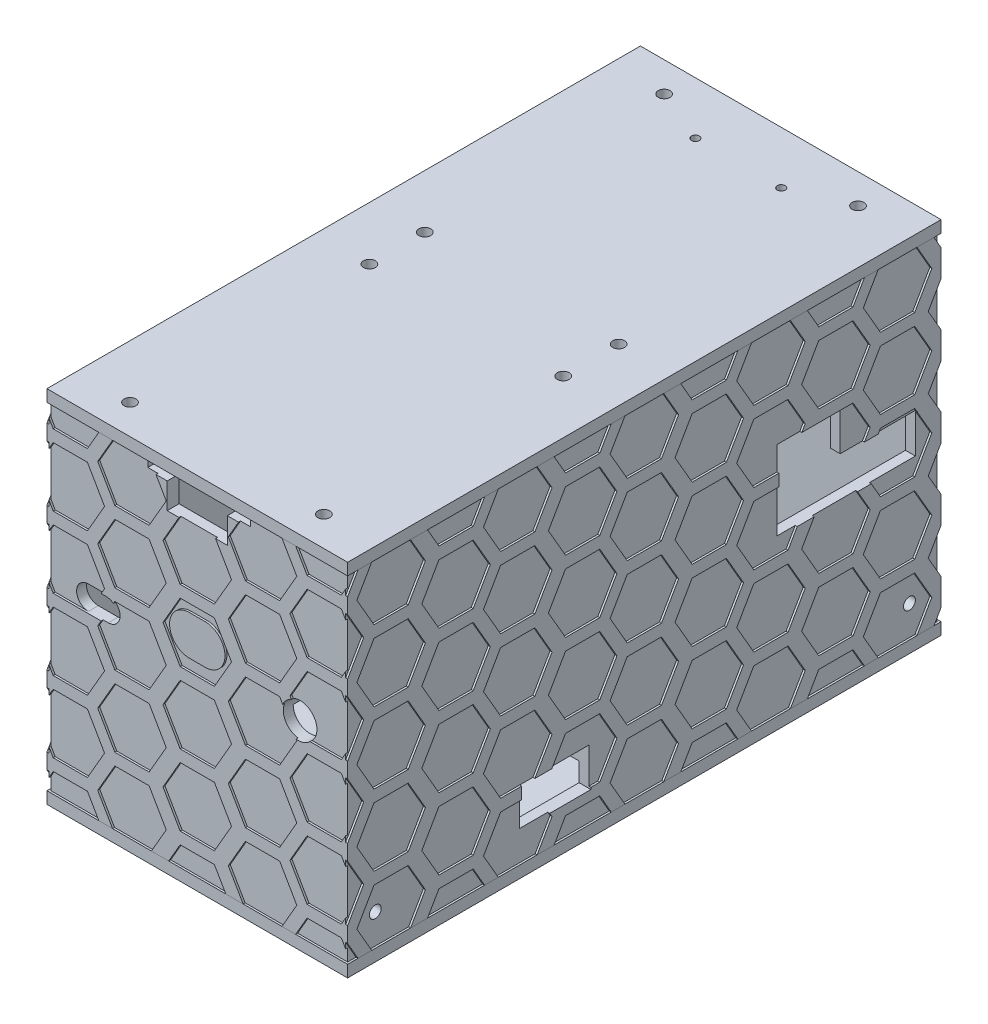
SolidWorks part; units mm, degrees
ref_plane "Front Plane" through (0, 0, 0) normal (0, 0, 1) x (1, 0, 0)
ref_plane "Top Plane" through (0, 0, 0) normal (0, 1, 0) x (1, 0, 0)
ref_plane "Right Plane" through (0, 0, 0) normal (1, 0, 0) x (0, 0, -1)
sketch "Sketch1" plane through (0, 0, 0) normal (0, 1, 0) x (1, 0, 0)
  line L0 (0, -67.5) -> (0, -72) construction
  line L1 (-38, 75) -> (38, 75)
  line L2 (-38, 75) -> (-38, -75)
  line L3 (-38, -75) -> (38, -75)
  line L4 (38, 75) -> (38, -75)
  line L5 (-38, 75) -> (38, -75) construction
  line L6 (-38, -75) -> (38, 75) construction
  line L7 (-24.5, -7) -> (24.5, -7) construction
  line L8 (-24.5, -7) -> (-24.5, -67.5) construction
  line L9 (-24.5, -67.5) -> (24.5, -67.5) construction
  line L10 (24.5, -7) -> (24.5, -67.5) construction
  line L11 (-24.5, -7) -> (24.5, -67.5) construction
  line L12 (-24.5, -67.5) -> (24.5, -7) construction
  line L13 (-35, -72) -> (35, -72) construction
  line L14 (-35, -72) -> (-35, 72) construction
  line L15 (-35, 72) -> (35, 72) construction
  line L16 (35, -72) -> (35, 72) construction
  line L17 (-35, -72) -> (35, 72) construction
  line L18 (-35, 72) -> (35, -72) construction
  line L19 (-35, 0) -> (35, 0) construction
  line L20 (-11.85, 61.75) -> (11.85, 61.75) construction
  line L21 (0, 61.75) -> (0, 75) construction
  line L22 (-10.85, 62.75) -> (-10.85, 75) construction
  circle A0 centre (-24.5, -7) radius 1.5
  circle A1 centre (24.5, -7) radius 1.5
  circle A2 centre (-24.5, -67.5) radius 1.5
  circle A3 centre (24.5, -67.5) radius 1.5
  circle A4 centre (-24.5, 67.5) radius 1.5
  circle A5 centre (24.5, 67.5) radius 1.5
  circle A6 centre (24.5, 7) radius 1.5
  circle A7 centre (-24.5, 7) radius 1.5
  circle A8 centre (-10.85, 61.75) radius 1
  circle A9 centre (10.85, 61.75) radius 1
  point P0 (0, 0)
  point P5 (0, -37.25)
  point P12 (0, 0)
  dimension "D9" = 3
  dimension "D10" = 2
  dimension "D8" = 23.7
  dimension "D11" = 2
  dimension "D1" = 76
  dimension "D2" = 150
  dimension "D3" = 49
  dimension "D4" = 60.5
  dimension "D5" = 3
  dimension "D6" = 3
  dimension "D7" = 4.5
  dimension "D12" = 12.25
extrude "Boss-Extrude1" add sketch "Sketch1" along normal blind 3
sketch "Sketch3" plane through (0, 0, 0) normal (0, -1, 0) x (1, 0, 0)
  line L0 (-38, 75) -> (-38, -75)
  line L1 (-38, 75) -> (38, 75)
  line L2 (38, 75) -> (38, -75)
  line L3 (38, -75) -> (-38, -75)
  line L4 (-35, 61.5) -> (-18.5, 61.5)
  line L5 (-18.5, 61.5) -> (-18.5, 72)
  line L6 (-18.5, 72) -> (18.5, 72)
  line L7 (18.5, 72) -> (18.5, 61.5)
  line L8 (18.5, 61.5) -> (35, 61.5)
  line L9 (35, 61.5) -> (35, 13)
  line L10 (35, 13) -> (18.5, 13)
  line L11 (18.5, 13) -> (18.5, -13)
  line L12 (18.5, -13) -> (35, -13)
  line L13 (35, -13) -> (35, -61.5)
  line L14 (35, -61.5) -> (18.5, -61.5)
  line L15 (18.5, -61.5) -> (18.5, -72)
  line L16 (18.5, -72) -> (-18.5, -72)
  line L17 (-18.5, -72) -> (-18.5, -61.5)
  line L18 (-18.5, -61.5) -> (-35, -61.5)
  line L19 (-35, -61.5) -> (-35, -13)
  line L20 (-35, -13) -> (-18.5, -13)
  line L21 (-18.5, -13) -> (-18.5, 13)
  line L22 (-18.5, 13) -> (-35, 13)
  line L23 (-35, 13) -> (-35, 61.5)
  circle A0 centre (-24.5, 67.5) radius 1.5 construction
  circle A1 centre (24.5, 67.5) radius 1.5 construction
  circle A2 centre (24.5, 7) radius 1.5 construction
  circle A3 centre (24.5, -7) radius 1.5 construction
  circle A4 centre (-24.5, 7) radius 1.5 construction
  circle A5 centre (-24.5, -7) radius 1.5 construction
  circle A6 centre (-24.5, -67.5) radius 1.5 construction
  circle A7 centre (24.5, -67.5) radius 1.5 construction
  circle A8 centre (-24.5, 67.5) radius 1.5
  circle A9 centre (24.5, 67.5) radius 1.5
  circle A10 centre (-24.5, 7) radius 1.5
  circle A11 centre (-24.5, -7) radius 1.5
  circle A12 centre (24.5, -7) radius 1.5
  circle A13 centre (24.5, 7) radius 1.5
  circle A14 centre (-24.5, -67.5) radius 1.5
  circle A19 centre (24.5, -67.5) radius 1.5
  dimension "D3" = 6
  dimension "D4" = 6
  dimension "D5" = 6
  dimension "D8" = 6
  dimension "D9" = 6
  dimension "D10" = 6
  dimension "D11" = 6
  dimension "D13" = 6
  dimension "D16" = 6
  dimension "D19" = 6
  dimension "D1" = 3
  dimension "D2" = 3
  dimension "D6" = 6
  dimension "D7" = 3
  dimension "D12" = 6
  dimension "D14" = 3
  dimension "D15" = 6
  dimension "D17" = 6
  dimension "D18" = 3
  dimension "D20" = 3
extrude "Boss-Extrude2" add sketch "Sketch3" along normal blind 3 separate body
sketch "Sketch4" plane through (0, -3, 0) normal (0, -1, 0) x (1, 0, 0)
  line L1 (38, 75) -> (38, -75)
  line L2 (38, -75) -> (-38, -75)
  line L3 (-38, -75) -> (-38, 75)
  line L4 (18.5, 72) -> (-18.5, 72)
  line L5 (-18.5, 72) -> (-35, 72)
  line L6 (-35, 72) -> (-35, 61.5)
  line L7 (-35, 61.5) -> (-35, -61.5)
  line L8 (-35, -61.5) -> (-35, -72)
  line L9 (-35, -72) -> (18.5, -72)
  line L10 (18.5, -72) -> (35, -72)
  line L11 (35, -72) -> (35, -61.5)
  line L12 (35, -61.5) -> (35, 61.5)
  line L13 (35, 61.5) -> (35, 72)
  line L14 (35, 72) -> (18.5, 72)
  line L15 (-38, 75) -> (38, 75)
extrude "Boss-Extrude3" add sketch "Sketch4" along normal blind 82
sketch "Sketch6" plane through (0, 0, -75) normal (0, 0, -1) x (-1, 0, 0)
  line L0 (0, 0) -> (0, -33) construction
  line L1 (-2, -33) -> (2, -33) construction
  line L2 (-2, -28) -> (2, -28)
  line L3 (-2, -38) -> (2, -38)
  line L4 (-2, -33) -> (-7, -33) construction
  line L5 (2, -33) -> (7, -33) construction
  arc A0 (-2, -28) -> (-2, -38) centre (-2, -33) ccw
  arc A1 (2, -38) -> (2, -28) centre (2, -33) ccw
  point P5 (0, -33)
  dimension "D1" = 10
  dimension "D2" = 14
  dimension "D3" = 28
extrude "Cut-Extrude1" cut sketch "Sketch6" against normal up to surface (3 mm away) up to face at (0, -22.75, -72)
sketch "Sketch7" plane through (0, 0, 75) normal (0, 0, 1) x (1, 0, 0)
  line L0 (0, 0) -> (13, 0)
  line L1 (-38, 0) -> (38, 0) construction
  line L2 (13, 0) -> (13, -2)
  line L3 (13, -2) -> (7.6, -2)
  line L4 (7.6, -2) -> (7.6, -8.5)
  line L5 (7.6, -8.5) -> (-7.6, -8.5)
  line L6 (-7.6, -8.5) -> (-7.6, -2)
  line L7 (-7.6, -2) -> (-13, -2)
  line L8 (-13, -2) -> (-13, 0)
  line L9 (38, 0) -> (-38, 0) construction
  line L10 (-13, 0) -> (0, 0)
  line L11 (0, 0) -> (0, -8.5) construction
  dimension "D1" = 15.2
  dimension "D2" = 6.5
  dimension "D3" = 2
  dimension "D4" = 5.4
extrude "Cut-Extrude2" cut sketch "Sketch7" against normal up to surface (3 mm away) up to face at (0, -22.75, 72)
sketch "Sketch8" plane through (38, 0, 0) normal (1, 0, 0) x (0, 0, -1)
  line L0 (-75, -85) -> (-75, 0) construction
  line L1 (-31, -68) -> (-13.5, -68)
  line L2 (-31, -68) -> (-31, -77.5)
  line L3 (-31, -77.5) -> (-13.5, -77.5)
  line L4 (-13.5, -68) -> (-13.5, -77.5)
  line L5 (-31, -68) -> (-13.5, -77.5) construction
  line L6 (-31, -77.5) -> (-13.5, -68) construction
  line L7 (-75, 0) -> (75, 0) construction
  point P0 (-22.25, -72.75)
  dimension "D1" = 44
  dimension "D2" = 68
  dimension "D3" = 17.5
  dimension "D4" = 9.5
extrude "Cut-Extrude3" cut sketch "Sketch8" against normal up to surface (3 mm away) up to face at (35, -15.6667, 0)
sketch "Sketch9" plane through (38, 0, 0) normal (1, 0, 0) x (0, 0, -1)
  line L0 (-31, -72.75) -> (-33, -72.75)
  line L1 (-31, -68) -> (-31, -77.5) construction
  line L2 (-33, -72.75) -> (-33, -66)
  line L3 (-33, -66) -> (-11.5, -66)
  line L4 (-11.5, -66) -> (-11.5, -72.75)
  line L5 (-11.5, -72.75) -> (-13.5, -72.75)
  line L6 (-13.5, -77.5) -> (-13.5, -68) construction
  line L7 (-13.5, -72.75) -> (-13.5, -68)
  line L8 (-13.5, -68) -> (-31, -68)
  line L9 (-31, -68) -> (-31, -72.75)
  dimension "D1" = 2
  dimension "D2" = 2
extrude "Boss-Extrude4" add sketch "Sketch9" against normal blind 10
sketch "Sketch12" plane through (0, 0, 75) normal (0, 0, 1) x (1, 0, 0)
  line L0 (-28, -35) -> (-23, -35)
  line L1 (-28, -41) -> (-23, -41)
  line L2 (-31, -38) -> (-20, -38) construction
  line L3 (-38, 0) -> (38, 0) construction
  line L4 (-25.5, 0) -> (-25.5, -35) construction
  line L5 (-13, 0) -> (-38, 0) construction
  line L6 (25.5, -38) -> (25.5, 0) construction
  line L7 (38, 0) -> (13, 0) construction
  arc A0 (-28, -35) -> (-28, -41) centre (-28, -38) ccw
  arc A1 (-23, -41) -> (-23, -35) centre (-23, -38) ccw
  circle A2 centre (25.5, -38) radius 4.25
  dimension "D1" = 6
  dimension "D4" = 8.5
  dimension "D2" = 11
  dimension "D3" = 35
extrude "Cut-Extrude4" cut sketch "Sketch12" against normal up to surface (3 mm away) up to face at (0, -12.9375, 72)
sketch "Sketch13" plane through (0, 0, 75) normal (0, 0, 1) x (1, 0, 0)
  line L0 (21.25, -38) -> (19.25, -38)
  line L1 (19.25, -38) -> (19.25, -31.75)
  line L2 (19.25, -31.75) -> (38, -31.75)
  line L3 (38, -85) -> (38, 0) construction
  line L4 (38, -31.75) -> (38, -38)
  line L5 (38, -38) -> (29.75, -38)
  line L6 (25.5, -33.75) -> (25.5, -31.75) construction
  circle A0 centre (25.5, -38) radius 4.25 construction
  arc A1 (29.75, -38) -> (21.25, -38) centre (25.5, -38) ccw
  dimension "D1" = 2
extrude "Boss-Extrude7" add sketch "Sketch13" against normal blind 10
ref_plane "Plane1" through (0, 0, 50) normal (0, 0, 1) x (1, 0, 0)
sketch "Sketch15" plane through (0, 0, 50) normal (0, 0, 1) x (1, 0, 0)
  line L0 (22.3, -38) -> (20.3, -38)
  line L1 (20.3, -38) -> (20.3, -32.8)
  line L2 (20.3, -32.8) -> (38, -32.8)
  line L3 (38, -85) -> (38, 0) construction
  line L4 (38, -32.8) -> (38, -38)
  line L5 (38, -38) -> (28.7, -38) construction
  line L6 (25.5, -34.8) -> (25.5, -32.8) construction
  line L10 (28.7, -38) -> (28.7, -43)
  line L11 (28.7, -43) -> (38, -43)
  line L12 (38, -43) -> (38, -38)
  arc A0 (28.7, -38) -> (22.3, -38) centre (25.5, -38) ccw
  circle A1 centre (25.5, -38) radius 4.25 construction
  dimension "D1" = 6.4
  dimension "D2" = 2
  dimension "D3" = 5
extrude "Boss-Extrude8" add sketch "Sketch15" against normal blind 2
chamfer "Chamfer1" distance 12 angle 45 1 edges at (35, -32.8, 49)
chamfer "Chamfer2" distance 2 angle 45 2 edges at (35, -31.9, 50) (35, -31.9, 48)
sketch "Sketch16" plane through (38, 0, 0) normal (1, 0, 0) x (0, 0, -1)
  line L0 (-67.5, -77.5) -> (-67.5, 0) construction
  line L1 (75, 0) -> (-75, 0) construction
  line L2 (-66, 0) -> (-69, 0) construction
  line L3 (69, 0) -> (66, 0) construction
  line L4 (75, -85) -> (-75, -85) construction
  line L5 (67.5, 0) -> (67.5, -77.5) construction
  line L6 (-67.5, -77.5) -> (67.5, -77.5) construction
  circle A0 centre (-67.5, -77.5) radius 1.5
  circle A1 centre (67.5, -77.5) radius 1.5
  dimension "D1" = 3
  dimension "D2" = 7.5
extrude "Cut-Extrude5" cut sketch "Sketch16" against normal through all and the other way through all
ref_plane "Plane2" through (0, 0, 0) normal (-1, 0, 0) x (0, 0, 1)
sketch "Sketch17" plane through (-38, 0, 0) normal (-1, 0, 0) x (0, 0, 1)
  line L0 (0, -42.5) -> (0, 0) construction
  line L1 (8.6603, -42.5) -> (4.3301, -35)
  line L2 (4.3301, -35) -> (-4.3301, -35)
  line L3 (-4.3301, -35) -> (-8.6603, -42.5)
  line L4 (-8.6603, -42.5) -> (-4.3301, -50)
  line L5 (-4.3301, -50) -> (4.3301, -50)
  line L6 (4.3301, -50) -> (8.6603, -42.5)
  line L7 (0, -42.5) -> (75, -42.5) construction
  line L8 (75, -85) -> (75, 0) construction
  line L9 (19.9186, -80) -> (24.2487, -87.5)
  line L10 (8.6603, -24.5) -> (4.3301, -17)
  line L11 (4.3301, -17) -> (-4.3301, -17)
  line L12 (-4.3301, -17) -> (-8.6603, -24.5)
  line L13 (-8.6603, -24.5) -> (-4.3301, -32)
  line L14 (-4.3301, -32) -> (4.3301, -32)
  line L15 (4.3301, -32) -> (8.6603, -24.5)
  line L16 (8.6603, -6.5) -> (4.3301, 1)
  line L17 (4.3301, 1) -> (-4.3301, 1)
  line L18 (-4.3301, 1) -> (-8.6603, -6.5)
  line L19 (-8.6603, -6.5) -> (-4.3301, -14)
  line L20 (-4.3301, -14) -> (4.3301, -14)
  line L21 (4.3301, -14) -> (8.6603, -6.5)
  line L22 (24.2487, -15.5) -> (19.9186, -8)
  line L23 (19.9186, -8) -> (11.2583, -8)
  line L24 (11.2583, -8) -> (6.9282, -15.5)
  line L25 (6.9282, -15.5) -> (11.2583, -23)
  line L26 (11.2583, -23) -> (19.9186, -23)
  line L27 (19.9186, -23) -> (24.2487, -15.5)
  line L28 (24.2487, -33.5) -> (19.9186, -26)
  line L29 (19.9186, -26) -> (11.2583, -26)
  line L30 (11.2583, -26) -> (6.9282, -33.5)
  line L31 (6.9282, -33.5) -> (11.2583, -41)
  line L32 (11.2583, -41) -> (19.9186, -41)
  line L33 (19.9186, -41) -> (24.2487, -33.5)
  line L34 (24.2487, 2.5) -> (19.9186, 10)
  line L35 (19.9186, 10) -> (11.2583, 10)
  line L36 (11.2583, 10) -> (6.9282, 2.5)
  line L37 (6.9282, 2.5) -> (11.2583, -5)
  line L38 (11.2583, -5) -> (19.9186, -5)
  line L39 (19.9186, -5) -> (24.2487, 2.5)
  line L40 (11.2583, -80) -> (19.9186, -80)
  line L41 (6.9282, -87.5) -> (11.2583, -80)
  line L42 (11.2583, -95) -> (6.9282, -87.5)
  line L43 (19.9186, -95) -> (11.2583, -95)
  line L44 (24.2487, -87.5) -> (19.9186, -95)
  line L45 (19.9186, -44) -> (24.2487, -51.5)
  line L46 (11.2583, -44) -> (19.9186, -44)
  line L47 (6.9282, -51.5) -> (11.2583, -44)
  line L48 (11.2583, -59) -> (6.9282, -51.5)
  line L49 (19.9186, -59) -> (11.2583, -59)
  line L50 (24.2487, -51.5) -> (19.9186, -59)
  line L51 (19.9186, -62) -> (24.2487, -69.5)
  line L52 (11.2583, -62) -> (19.9186, -62)
  line L53 (6.9282, -69.5) -> (11.2583, -62)
  line L54 (11.2583, -77) -> (6.9282, -69.5)
  line L55 (19.9186, -77) -> (11.2583, -77)
  line L56 (24.2487, -69.5) -> (19.9186, -77)
  line L57 (4.3301, -71) -> (8.6603, -78.5)
  line L58 (-4.3301, -71) -> (4.3301, -71)
  line L59 (-8.6603, -78.5) -> (-4.3301, -71)
  line L60 (-4.3301, -86) -> (-8.6603, -78.5)
  line L61 (4.3301, -86) -> (-4.3301, -86)
  line L62 (8.6603, -78.5) -> (4.3301, -86)
  line L63 (4.3301, -53) -> (8.6603, -60.5)
  line L64 (-4.3301, -53) -> (4.3301, -53)
  line L65 (-8.6603, -60.5) -> (-4.3301, -53)
  line L66 (-4.3301, -68) -> (-8.6603, -60.5)
  line L67 (4.3301, -68) -> (-4.3301, -68)
  line L68 (8.6603, -60.5) -> (4.3301, -68)
  line L69 (51.9186, 10) -> (43.2583, 10)
  line L70 (56.2487, 2.5) -> (51.9186, 10)
  line L71 (51.9186, -5) -> (56.2487, 2.5)
  line L72 (36.3301, 1) -> (27.6699, 1)
  line L73 (40.6603, -6.5) -> (36.3301, 1)
  line L74 (27.6699, 1) -> (23.3397, -6.5)
  line L75 (36.3301, -14) -> (40.6603, -6.5)
  line L76 (43.2583, 10) -> (38.9282, 2.5)
  line L77 (38.9282, 2.5) -> (43.2583, -5)
  line L78 (43.2583, -5) -> (51.9186, -5)
  line L79 (23.3397, -6.5) -> (27.6699, -14)
  line L80 (27.6699, -14) -> (36.3301, -14)
  line L81 (51.9186, -8) -> (43.2583, -8)
  line L82 (43.2583, -8) -> (38.9282, -15.5)
  line L83 (38.9282, -15.5) -> (43.2583, -23)
  line L84 (43.2583, -23) -> (51.9186, -23)
  line L85 (51.9186, -23) -> (56.2487, -15.5)
  line L86 (56.2487, -15.5) -> (51.9186, -8)
  line L87 (36.3301, -17) -> (27.6699, -17)
  line L88 (40.6603, -24.5) -> (36.3301, -17)
  line L89 (27.6699, -17) -> (23.3397, -24.5)
  line L90 (23.3397, -24.5) -> (27.6699, -32)
  line L91 (27.6699, -32) -> (36.3301, -32)
  line L92 (36.3301, -32) -> (40.6603, -24.5)
  line L93 (43.2583, -26) -> (38.9282, -33.5)
  line L94 (38.9282, -33.5) -> (43.2583, -41)
  line L95 (51.9186, -26) -> (43.2583, -26)
  line L96 (56.2487, -33.5) -> (51.9186, -26)
  line L97 (51.9186, -41) -> (56.2487, -33.5)
  line L98 (43.2583, -41) -> (51.9186, -41)
  line L99 (40.6603, -42.5) -> (36.3301, -35)
  line L100 (36.3301, -35) -> (27.6699, -35)
  line L101 (27.6699, -35) -> (23.3397, -42.5)
  line L102 (23.3397, -42.5) -> (27.6699, -50)
  line L103 (43.2583, -44) -> (51.9186, -44)
  line L104 (36.3301, -50) -> (40.6603, -42.5)
  line L105 (27.6699, -50) -> (36.3301, -50)
  line L106 (38.9282, -51.5) -> (43.2583, -44)
  line L107 (43.2583, -59) -> (38.9282, -51.5)
  line L108 (51.9186, -59) -> (43.2583, -59)
  line L109 (56.2487, -51.5) -> (51.9186, -59)
  line L110 (51.9186, -44) -> (56.2487, -51.5)
  line L111 (36.3301, -53) -> (40.6603, -60.5)
  line L112 (27.6699, -53) -> (36.3301, -53)
  line L113 (23.3397, -60.5) -> (27.6699, -53)
  line L114 (27.6699, -68) -> (23.3397, -60.5)
  line L115 (36.3301, -68) -> (27.6699, -68)
  line L116 (40.6603, -60.5) -> (36.3301, -68)
  line L117 (43.2583, -62) -> (51.9186, -62)
  line L118 (38.9282, -69.5) -> (43.2583, -62)
  line L119 (51.9186, -62) -> (56.2487, -69.5)
  line L120 (56.2487, -69.5) -> (51.9186, -77)
  line L121 (51.9186, -77) -> (43.2583, -77)
  line L122 (43.2583, -77) -> (38.9282, -69.5)
  line L123 (36.3301, -71) -> (40.6603, -78.5)
  line L124 (27.6699, -71) -> (36.3301, -71)
  line L125 (23.3397, -78.5) -> (27.6699, -71)
  line L126 (27.6699, -86) -> (23.3397, -78.5)
  line L127 (36.3301, -86) -> (27.6699, -86)
  line L128 (40.6603, -78.5) -> (36.3301, -86)
  line L129 (38.9282, -87.5) -> (43.2583, -80)
  line L130 (43.2583, -95) -> (38.9282, -87.5)
  line L131 (51.9186, -95) -> (43.2583, -95)
  line L132 (56.2487, -87.5) -> (51.9186, -95)
  line L133 (51.9186, -80) -> (56.2487, -87.5)
  line L134 (43.2583, -80) -> (51.9186, -80)
  line L135 (83.9186, 10) -> (75.2583, 10)
  line L136 (88.2487, 2.5) -> (83.9186, 10)
  line L137 (83.9186, -5) -> (88.2487, 2.5)
  line L138 (68.3301, 1) -> (59.6699, 1)
  line L139 (72.6603, -6.5) -> (68.3301, 1)
  line L140 (59.6699, 1) -> (55.3397, -6.5)
  line L141 (68.3301, -14) -> (72.6603, -6.5)
  line L142 (75.2583, 10) -> (70.9282, 2.5)
  line L143 (70.9282, 2.5) -> (75.2583, -5)
  line L144 (75.2583, -5) -> (83.9186, -5)
  line L145 (55.3397, -6.5) -> (59.6699, -14)
  line L146 (59.6699, -14) -> (68.3301, -14)
  line L147 (83.9186, -8) -> (75.2583, -8)
  line L148 (75.2583, -8) -> (70.9282, -15.5)
  line L149 (70.9282, -15.5) -> (75.2583, -23)
  line L150 (75.2583, -23) -> (83.9186, -23)
  line L151 (83.9186, -23) -> (88.2487, -15.5)
  line L152 (88.2487, -15.5) -> (83.9186, -8)
  line L153 (68.3301, -17) -> (59.6699, -17)
  line L154 (72.6603, -24.5) -> (68.3301, -17)
  line L155 (59.6699, -17) -> (55.3397, -24.5)
  line L156 (55.3397, -24.5) -> (59.6699, -32)
  line L157 (59.6699, -32) -> (68.3301, -32)
  line L158 (68.3301, -32) -> (72.6603, -24.5)
  line L159 (75.2583, -26) -> (70.9282, -33.5)
  line L160 (70.9282, -33.5) -> (75.2583, -41)
  line L161 (83.9186, -26) -> (75.2583, -26)
  line L162 (88.2487, -33.5) -> (83.9186, -26)
  line L163 (83.9186, -41) -> (88.2487, -33.5)
  line L164 (75.2583, -41) -> (83.9186, -41)
  line L165 (72.6603, -42.5) -> (68.3301, -35)
  line L166 (68.3301, -35) -> (59.6699, -35)
  line L167 (59.6699, -35) -> (55.3397, -42.5)
  line L168 (55.3397, -42.5) -> (59.6699, -50)
  line L169 (75.2583, -44) -> (83.9186, -44)
  line L170 (68.3301, -50) -> (72.6603, -42.5)
  line L171 (59.6699, -50) -> (68.3301, -50)
  line L172 (70.9282, -51.5) -> (75.2583, -44)
  line L173 (75.2583, -59) -> (70.9282, -51.5)
  line L174 (83.9186, -59) -> (75.2583, -59)
  line L175 (88.2487, -51.5) -> (83.9186, -59)
  line L176 (83.9186, -44) -> (88.2487, -51.5)
  line L177 (68.3301, -53) -> (72.6603, -60.5)
  line L178 (59.6699, -53) -> (68.3301, -53)
  line L179 (55.3397, -60.5) -> (59.6699, -53)
  line L180 (59.6699, -68) -> (55.3397, -60.5)
  line L181 (68.3301, -68) -> (59.6699, -68)
  line L182 (72.6603, -60.5) -> (68.3301, -68)
  line L183 (75.2583, -62) -> (83.9186, -62)
  line L184 (70.9282, -69.5) -> (75.2583, -62)
  line L185 (83.9186, -62) -> (88.2487, -69.5)
  line L186 (88.2487, -69.5) -> (83.9186, -77)
  line L187 (83.9186, -77) -> (75.2583, -77)
  line L188 (75.2583, -77) -> (70.9282, -69.5)
  line L189 (68.3301, -71) -> (72.6603, -78.5)
  line L190 (59.6699, -71) -> (68.3301, -71)
  line L191 (55.3397, -78.5) -> (59.6699, -71)
  line L192 (59.6699, -86) -> (55.3397, -78.5)
  line L193 (68.3301, -86) -> (59.6699, -86)
  line L194 (72.6603, -78.5) -> (68.3301, -86)
  line L195 (70.9282, -87.5) -> (75.2583, -80)
  line L196 (75.2583, -95) -> (70.9282, -87.5)
  line L197 (83.9186, -95) -> (75.2583, -95)
  line L198 (88.2487, -87.5) -> (83.9186, -95)
  line L199 (83.9186, -80) -> (88.2487, -87.5)
  line L200 (75.2583, -80) -> (83.9186, -80)
  line L201 (19.9186, 10) -> (11.2583, 10)
  line L202 (24.2487, 2.5) -> (19.9186, 10)
  line L203 (19.9186, -5) -> (24.2487, 2.5)
  line L204 (4.3301, 1) -> (-4.3301, 1)
  line L205 (8.6603, -6.5) -> (4.3301, 1)
  line L206 (-4.3301, 1) -> (-8.6603, -6.5)
  line L207 (4.3301, -14) -> (8.6603, -6.5)
  line L208 (11.2583, 10) -> (6.9282, 2.5)
  line L209 (6.9282, 2.5) -> (11.2583, -5)
  line L210 (11.2583, -5) -> (19.9186, -5)
  line L211 (-8.6603, -6.5) -> (-4.3301, -14)
  line L212 (-4.3301, -14) -> (4.3301, -14)
  line L213 (19.9186, -8) -> (11.2583, -8)
  line L214 (11.2583, -8) -> (6.9282, -15.5)
  line L215 (6.9282, -15.5) -> (11.2583, -23)
  line L216 (11.2583, -23) -> (19.9186, -23)
  line L217 (19.9186, -23) -> (24.2487, -15.5)
  line L218 (24.2487, -15.5) -> (19.9186, -8)
  line L219 (4.3301, -17) -> (-4.3301, -17)
  line L220 (8.6603, -24.5) -> (4.3301, -17)
  line L221 (-4.3301, -17) -> (-8.6603, -24.5)
  line L222 (-8.6603, -24.5) -> (-4.3301, -32)
  line L223 (-4.3301, -32) -> (4.3301, -32)
  line L224 (4.3301, -32) -> (8.6603, -24.5)
  line L225 (11.2583, -26) -> (6.9282, -33.5)
  line L226 (6.9282, -33.5) -> (11.2583, -41)
  line L227 (19.9186, -26) -> (11.2583, -26)
  line L228 (24.2487, -33.5) -> (19.9186, -26)
  line L229 (19.9186, -41) -> (24.2487, -33.5)
  line L230 (11.2583, -41) -> (19.9186, -41)
  line L231 (8.6603, -42.5) -> (4.3301, -35)
  line L232 (4.3301, -35) -> (-4.3301, -35)
  line L233 (-4.3301, -35) -> (-8.6603, -42.5)
  line L234 (-8.6603, -42.5) -> (-4.3301, -50)
  line L235 (11.2583, -44) -> (19.9186, -44)
  line L236 (4.3301, -50) -> (8.6603, -42.5)
  line L237 (-4.3301, -50) -> (4.3301, -50)
  line L238 (6.9282, -51.5) -> (11.2583, -44)
  line L239 (11.2583, -59) -> (6.9282, -51.5)
  line L240 (19.9186, -59) -> (11.2583, -59)
  line L241 (24.2487, -51.5) -> (19.9186, -59)
  line L242 (19.9186, -44) -> (24.2487, -51.5)
  line L243 (4.3301, -53) -> (8.6603, -60.5)
  line L244 (-4.3301, -53) -> (4.3301, -53)
  line L245 (-8.6603, -60.5) -> (-4.3301, -53)
  line L246 (-4.3301, -68) -> (-8.6603, -60.5)
  line L247 (4.3301, -68) -> (-4.3301, -68)
  line L248 (8.6603, -60.5) -> (4.3301, -68)
  line L249 (11.2583, -62) -> (19.9186, -62)
  line L250 (6.9282, -69.5) -> (11.2583, -62)
  line L251 (19.9186, -62) -> (24.2487, -69.5)
  line L252 (24.2487, -69.5) -> (19.9186, -77)
  line L253 (19.9186, -77) -> (11.2583, -77)
  line L254 (11.2583, -77) -> (6.9282, -69.5)
  line L255 (4.3301, -71) -> (8.6603, -78.5)
  line L256 (-4.3301, -71) -> (4.3301, -71)
  line L257 (-8.6603, -78.5) -> (-4.3301, -71)
  line L258 (-4.3301, -86) -> (-8.6603, -78.5)
  line L259 (4.3301, -86) -> (-4.3301, -86)
  line L260 (8.6603, -78.5) -> (4.3301, -86)
  line L261 (6.9282, -87.5) -> (11.2583, -80)
  line L262 (11.2583, -95) -> (6.9282, -87.5)
  line L263 (19.9186, -95) -> (11.2583, -95)
  line L264 (24.2487, -87.5) -> (19.9186, -95)
  line L265 (19.9186, -80) -> (24.2487, -87.5)
  line L266 (11.2583, -80) -> (19.9186, -80)
  line L267 (51.9186, 10) -> (43.2583, 10)
  line L268 (56.2487, 2.5) -> (51.9186, 10)
  line L269 (51.9186, -5) -> (56.2487, 2.5)
  line L270 (36.3301, 1) -> (27.6699, 1)
  line L271 (40.6603, -6.5) -> (36.3301, 1)
  line L272 (27.6699, 1) -> (23.3397, -6.5)
  line L273 (36.3301, -14) -> (40.6603, -6.5)
  line L274 (43.2583, 10) -> (38.9282, 2.5)
  line L275 (38.9282, 2.5) -> (43.2583, -5)
  line L276 (43.2583, -5) -> (51.9186, -5)
  line L277 (23.3397, -6.5) -> (27.6699, -14)
  line L278 (27.6699, -14) -> (36.3301, -14)
  line L279 (51.9186, -8) -> (43.2583, -8)
  line L280 (43.2583, -8) -> (38.9282, -15.5)
  line L281 (38.9282, -15.5) -> (43.2583, -23)
  line L282 (43.2583, -23) -> (51.9186, -23)
  line L283 (51.9186, -23) -> (56.2487, -15.5)
  line L284 (56.2487, -15.5) -> (51.9186, -8)
  line L285 (36.3301, -17) -> (27.6699, -17)
  line L286 (40.6603, -24.5) -> (36.3301, -17)
  line L287 (27.6699, -17) -> (23.3397, -24.5)
  line L288 (23.3397, -24.5) -> (27.6699, -32)
  line L289 (27.6699, -32) -> (36.3301, -32)
  line L290 (36.3301, -32) -> (40.6603, -24.5)
  line L291 (43.2583, -26) -> (38.9282, -33.5)
  line L292 (38.9282, -33.5) -> (43.2583, -41)
  line L293 (51.9186, -26) -> (43.2583, -26)
  line L294 (56.2487, -33.5) -> (51.9186, -26)
  line L295 (51.9186, -41) -> (56.2487, -33.5)
  line L296 (43.2583, -41) -> (51.9186, -41)
  line L297 (40.6603, -42.5) -> (36.3301, -35)
  line L298 (36.3301, -35) -> (27.6699, -35)
  line L299 (27.6699, -35) -> (23.3397, -42.5)
  line L300 (23.3397, -42.5) -> (27.6699, -50)
  line L301 (43.2583, -44) -> (51.9186, -44)
  line L302 (36.3301, -50) -> (40.6603, -42.5)
  line L303 (27.6699, -50) -> (36.3301, -50)
  line L304 (38.9282, -51.5) -> (43.2583, -44)
  line L305 (43.2583, -59) -> (38.9282, -51.5)
  line L306 (51.9186, -59) -> (43.2583, -59)
  line L307 (56.2487, -51.5) -> (51.9186, -59)
  line L308 (51.9186, -44) -> (56.2487, -51.5)
  line L309 (36.3301, -53) -> (40.6603, -60.5)
  line L310 (27.6699, -53) -> (36.3301, -53)
  line L311 (23.3397, -60.5) -> (27.6699, -53)
  line L312 (27.6699, -68) -> (23.3397, -60.5)
  line L313 (36.3301, -68) -> (27.6699, -68)
  line L314 (40.6603, -60.5) -> (36.3301, -68)
  line L315 (43.2583, -62) -> (51.9186, -62)
  line L316 (38.9282, -69.5) -> (43.2583, -62)
  line L317 (51.9186, -62) -> (56.2487, -69.5)
  line L318 (56.2487, -69.5) -> (51.9186, -77)
  line L319 (51.9186, -77) -> (43.2583, -77)
  line L320 (43.2583, -77) -> (38.9282, -69.5)
  line L321 (36.3301, -71) -> (40.6603, -78.5)
  line L322 (27.6699, -71) -> (36.3301, -71)
  line L323 (23.3397, -78.5) -> (27.6699, -71)
  line L324 (27.6699, -86) -> (23.3397, -78.5)
  line L325 (36.3301, -86) -> (27.6699, -86)
  line L326 (40.6603, -78.5) -> (36.3301, -86)
  line L327 (38.9282, -87.5) -> (43.2583, -80)
  line L328 (43.2583, -95) -> (38.9282, -87.5)
  line L329 (51.9186, -95) -> (43.2583, -95)
  line L330 (56.2487, -87.5) -> (51.9186, -95)
  line L331 (51.9186, -80) -> (56.2487, -87.5)
  line L332 (43.2583, -80) -> (51.9186, -80)
  line L333 (-12.0814, 10) -> (-20.7417, 10)
  line L334 (-7.7513, 2.5) -> (-12.0814, 10)
  line L335 (-12.0814, -5) -> (-7.7513, 2.5)
  line L336 (-27.6699, 1) -> (-36.3301, 1)
  line L337 (-23.3397, -6.5) -> (-27.6699, 1)
  line L338 (-36.3301, 1) -> (-40.6603, -6.5)
  line L339 (-27.6699, -14) -> (-23.3397, -6.5)
  line L340 (-20.7417, 10) -> (-25.0718, 2.5)
  line L341 (-25.0718, 2.5) -> (-20.7417, -5)
  line L342 (-20.7417, -5) -> (-12.0814, -5)
  line L343 (-40.6603, -6.5) -> (-36.3301, -14)
  line L344 (-36.3301, -14) -> (-27.6699, -14)
  line L345 (-12.0814, -8) -> (-20.7417, -8)
  line L346 (-20.7417, -8) -> (-25.0718, -15.5)
  line L347 (-25.0718, -15.5) -> (-20.7417, -23)
  line L348 (-20.7417, -23) -> (-12.0814, -23)
  line L349 (-12.0814, -23) -> (-7.7513, -15.5)
  line L350 (-7.7513, -15.5) -> (-12.0814, -8)
  line L351 (-27.6699, -17) -> (-36.3301, -17)
  line L352 (-23.3397, -24.5) -> (-27.6699, -17)
  line L353 (-36.3301, -17) -> (-40.6603, -24.5)
  line L354 (-40.6603, -24.5) -> (-36.3301, -32)
  line L355 (-36.3301, -32) -> (-27.6699, -32)
  line L356 (-27.6699, -32) -> (-23.3397, -24.5)
  line L357 (-20.7417, -26) -> (-25.0718, -33.5)
  line L358 (-25.0718, -33.5) -> (-20.7417, -41)
  line L359 (-12.0814, -26) -> (-20.7417, -26)
  line L360 (-7.7513, -33.5) -> (-12.0814, -26)
  line L361 (-12.0814, -41) -> (-7.7513, -33.5)
  line L362 (-20.7417, -41) -> (-12.0814, -41)
  line L363 (-23.3397, -42.5) -> (-27.6699, -35)
  line L364 (-27.6699, -35) -> (-36.3301, -35)
  line L365 (-36.3301, -35) -> (-40.6603, -42.5)
  line L366 (-40.6603, -42.5) -> (-36.3301, -50)
  line L367 (-20.7417, -44) -> (-12.0814, -44)
  line L368 (-27.6699, -50) -> (-23.3397, -42.5)
  line L369 (-36.3301, -50) -> (-27.6699, -50)
  line L370 (-25.0718, -51.5) -> (-20.7417, -44)
  line L371 (-20.7417, -59) -> (-25.0718, -51.5)
  line L372 (-12.0814, -59) -> (-20.7417, -59)
  line L373 (-7.7513, -51.5) -> (-12.0814, -59)
  line L374 (-12.0814, -44) -> (-7.7513, -51.5)
  line L375 (-27.6699, -53) -> (-23.3397, -60.5)
  line L376 (-36.3301, -53) -> (-27.6699, -53)
  line L377 (-40.6603, -60.5) -> (-36.3301, -53)
  line L378 (-36.3301, -68) -> (-40.6603, -60.5)
  line L379 (-27.6699, -68) -> (-36.3301, -68)
  line L380 (-23.3397, -60.5) -> (-27.6699, -68)
  line L381 (-20.7417, -62) -> (-12.0814, -62)
  line L382 (-25.0718, -69.5) -> (-20.7417, -62)
  line L383 (-12.0814, -62) -> (-7.7513, -69.5)
  line L384 (-7.7513, -69.5) -> (-12.0814, -77)
  line L385 (-12.0814, -77) -> (-20.7417, -77)
  line L386 (-20.7417, -77) -> (-25.0718, -69.5)
  line L387 (-27.6699, -71) -> (-23.3397, -78.5)
  line L388 (-36.3301, -71) -> (-27.6699, -71)
  line L389 (-40.6603, -78.5) -> (-36.3301, -71)
  line L390 (-36.3301, -86) -> (-40.6603, -78.5)
  line L391 (-27.6699, -86) -> (-36.3301, -86)
  line L392 (-23.3397, -78.5) -> (-27.6699, -86)
  line L393 (-25.0718, -87.5) -> (-20.7417, -80)
  line L394 (-20.7417, -95) -> (-25.0718, -87.5)
  line L395 (-12.0814, -95) -> (-20.7417, -95)
  line L396 (-7.7513, -87.5) -> (-12.0814, -95)
  line L397 (-12.0814, -80) -> (-7.7513, -87.5)
  line L398 (-20.7417, -80) -> (-12.0814, -80)
  line L399 (19.9186, 10) -> (11.2583, 10)
  line L400 (24.2487, 2.5) -> (19.9186, 10)
  line L401 (19.9186, -5) -> (24.2487, 2.5)
  line L402 (4.3301, 1) -> (-4.3301, 1)
  line L403 (8.6603, -6.5) -> (4.3301, 1)
  line L404 (-4.3301, 1) -> (-8.6603, -6.5)
  line L405 (4.3301, -14) -> (8.6603, -6.5)
  line L406 (11.2583, 10) -> (6.9282, 2.5)
  line L407 (6.9282, 2.5) -> (11.2583, -5)
  line L408 (11.2583, -5) -> (19.9186, -5)
  line L409 (-8.6603, -6.5) -> (-4.3301, -14)
  line L410 (-4.3301, -14) -> (4.3301, -14)
  line L411 (19.9186, -8) -> (11.2583, -8)
  line L412 (11.2583, -8) -> (6.9282, -15.5)
  line L413 (6.9282, -15.5) -> (11.2583, -23)
  line L414 (11.2583, -23) -> (19.9186, -23)
  line L415 (19.9186, -23) -> (24.2487, -15.5)
  line L416 (24.2487, -15.5) -> (19.9186, -8)
  line L417 (4.3301, -17) -> (-4.3301, -17)
  line L418 (8.6603, -24.5) -> (4.3301, -17)
  line L419 (-4.3301, -17) -> (-8.6603, -24.5)
  line L420 (-8.6603, -24.5) -> (-4.3301, -32)
  line L421 (-4.3301, -32) -> (4.3301, -32)
  line L422 (4.3301, -32) -> (8.6603, -24.5)
  line L423 (11.2583, -26) -> (6.9282, -33.5)
  line L424 (6.9282, -33.5) -> (11.2583, -41)
  line L425 (19.9186, -26) -> (11.2583, -26)
  line L426 (24.2487, -33.5) -> (19.9186, -26)
  line L427 (19.9186, -41) -> (24.2487, -33.5)
  line L428 (11.2583, -41) -> (19.9186, -41)
  line L429 (8.6603, -42.5) -> (4.3301, -35)
  line L430 (4.3301, -35) -> (-4.3301, -35)
  line L431 (-4.3301, -35) -> (-8.6603, -42.5)
  line L432 (-8.6603, -42.5) -> (-4.3301, -50)
  line L433 (11.2583, -44) -> (19.9186, -44)
  line L434 (4.3301, -50) -> (8.6603, -42.5)
  line L435 (-4.3301, -50) -> (4.3301, -50)
  line L436 (6.9282, -51.5) -> (11.2583, -44)
  line L437 (11.2583, -59) -> (6.9282, -51.5)
  line L438 (19.9186, -59) -> (11.2583, -59)
  line L439 (24.2487, -51.5) -> (19.9186, -59)
  line L440 (19.9186, -44) -> (24.2487, -51.5)
  line L441 (4.3301, -53) -> (8.6603, -60.5)
  line L442 (-4.3301, -53) -> (4.3301, -53)
  line L443 (-8.6603, -60.5) -> (-4.3301, -53)
  line L444 (-4.3301, -68) -> (-8.6603, -60.5)
  line L445 (4.3301, -68) -> (-4.3301, -68)
  line L446 (8.6603, -60.5) -> (4.3301, -68)
  line L447 (11.2583, -62) -> (19.9186, -62)
  line L448 (6.9282, -69.5) -> (11.2583, -62)
  line L449 (19.9186, -62) -> (24.2487, -69.5)
  line L450 (24.2487, -69.5) -> (19.9186, -77)
  line L451 (19.9186, -77) -> (11.2583, -77)
  line L452 (11.2583, -77) -> (6.9282, -69.5)
  line L453 (4.3301, -71) -> (8.6603, -78.5)
  line L454 (-4.3301, -71) -> (4.3301, -71)
  line L455 (-8.6603, -78.5) -> (-4.3301, -71)
  line L456 (-4.3301, -86) -> (-8.6603, -78.5)
  line L457 (4.3301, -86) -> (-4.3301, -86)
  line L458 (8.6603, -78.5) -> (4.3301, -86)
  line L459 (6.9282, -87.5) -> (11.2583, -80)
  line L460 (11.2583, -95) -> (6.9282, -87.5)
  line L461 (19.9186, -95) -> (11.2583, -95)
  line L462 (24.2487, -87.5) -> (19.9186, -95)
  line L463 (19.9186, -80) -> (24.2487, -87.5)
  line L464 (11.2583, -80) -> (19.9186, -80)
  line L465 (-44.0814, 10) -> (-52.7417, 10)
  line L466 (-39.7513, 2.5) -> (-44.0814, 10)
  line L467 (-44.0814, -5) -> (-39.7513, 2.5)
  line L468 (-59.6699, 1) -> (-68.3301, 1)
  line L469 (-55.3397, -6.5) -> (-59.6699, 1)
  line L470 (-68.3301, 1) -> (-72.6603, -6.5)
  line L471 (-59.6699, -14) -> (-55.3397, -6.5)
  line L472 (-52.7417, 10) -> (-57.0718, 2.5)
  line L473 (-57.0718, 2.5) -> (-52.7417, -5)
  line L474 (-52.7417, -5) -> (-44.0814, -5)
  line L475 (-72.6603, -6.5) -> (-68.3301, -14)
  line L476 (-68.3301, -14) -> (-59.6699, -14)
  line L477 (-44.0814, -8) -> (-52.7417, -8)
  line L478 (-52.7417, -8) -> (-57.0718, -15.5)
  line L479 (-57.0718, -15.5) -> (-52.7417, -23)
  line L480 (-52.7417, -23) -> (-44.0814, -23)
  line L481 (-44.0814, -23) -> (-39.7513, -15.5)
  line L482 (-39.7513, -15.5) -> (-44.0814, -8)
  line L483 (-59.6699, -17) -> (-68.3301, -17)
  line L484 (-55.3397, -24.5) -> (-59.6699, -17)
  line L485 (-68.3301, -17) -> (-72.6603, -24.5)
  line L486 (-72.6603, -24.5) -> (-68.3301, -32)
  line L487 (-68.3301, -32) -> (-59.6699, -32)
  line L488 (-59.6699, -32) -> (-55.3397, -24.5)
  line L489 (-52.7417, -26) -> (-57.0718, -33.5)
  line L490 (-57.0718, -33.5) -> (-52.7417, -41)
  line L491 (-44.0814, -26) -> (-52.7417, -26)
  line L492 (-39.7513, -33.5) -> (-44.0814, -26)
  line L493 (-44.0814, -41) -> (-39.7513, -33.5)
  line L494 (-52.7417, -41) -> (-44.0814, -41)
  line L495 (-55.3397, -42.5) -> (-59.6699, -35)
  line L496 (-59.6699, -35) -> (-68.3301, -35)
  line L497 (-68.3301, -35) -> (-72.6603, -42.5)
  line L498 (-72.6603, -42.5) -> (-68.3301, -50)
  line L499 (-52.7417, -44) -> (-44.0814, -44)
  line L500 (-59.6699, -50) -> (-55.3397, -42.5)
  line L501 (-68.3301, -50) -> (-59.6699, -50)
  line L502 (-57.0718, -51.5) -> (-52.7417, -44)
  line L503 (-52.7417, -59) -> (-57.0718, -51.5)
  line L504 (-44.0814, -59) -> (-52.7417, -59)
  line L505 (-39.7513, -51.5) -> (-44.0814, -59)
  line L506 (-44.0814, -44) -> (-39.7513, -51.5)
  line L507 (-59.6699, -53) -> (-55.3397, -60.5)
  line L508 (-68.3301, -53) -> (-59.6699, -53)
  line L509 (-72.6603, -60.5) -> (-68.3301, -53)
  line L510 (-68.3301, -68) -> (-72.6603, -60.5)
  line L511 (-59.6699, -68) -> (-68.3301, -68)
  line L512 (-55.3397, -60.5) -> (-59.6699, -68)
  line L513 (-52.7417, -62) -> (-44.0814, -62)
  line L514 (-57.0718, -69.5) -> (-52.7417, -62)
  line L515 (-44.0814, -62) -> (-39.7513, -69.5)
  line L516 (-39.7513, -69.5) -> (-44.0814, -77)
  line L517 (-44.0814, -77) -> (-52.7417, -77)
  line L518 (-52.7417, -77) -> (-57.0718, -69.5)
  line L519 (-59.6699, -71) -> (-55.3397, -78.5)
  line L520 (-68.3301, -71) -> (-59.6699, -71)
  line L521 (-72.6603, -78.5) -> (-68.3301, -71)
  line L522 (-68.3301, -86) -> (-72.6603, -78.5)
  line L523 (-59.6699, -86) -> (-68.3301, -86)
  line L524 (-55.3397, -78.5) -> (-59.6699, -86)
  line L525 (-57.0718, -87.5) -> (-52.7417, -80)
  line L526 (-52.7417, -95) -> (-57.0718, -87.5)
  line L527 (-44.0814, -95) -> (-52.7417, -95)
  line L528 (-39.7513, -87.5) -> (-44.0814, -95)
  line L529 (-44.0814, -80) -> (-39.7513, -87.5)
  line L530 (-52.7417, -80) -> (-44.0814, -80)
  line L531 (-12.0814, 10) -> (-20.7417, 10)
  line L532 (-7.7513, 2.5) -> (-12.0814, 10)
  line L533 (-12.0814, -5) -> (-7.7513, 2.5)
  line L534 (-27.6699, 1) -> (-36.3301, 1)
  line L535 (-23.3397, -6.5) -> (-27.6699, 1)
  line L536 (-36.3301, 1) -> (-40.6603, -6.5)
  line L537 (-27.6699, -14) -> (-23.3397, -6.5)
  line L538 (-20.7417, 10) -> (-25.0718, 2.5)
  line L539 (-25.0718, 2.5) -> (-20.7417, -5)
  line L540 (-20.7417, -5) -> (-12.0814, -5)
  line L541 (-40.6603, -6.5) -> (-36.3301, -14)
  line L542 (-36.3301, -14) -> (-27.6699, -14)
  line L543 (-12.0814, -8) -> (-20.7417, -8)
  line L544 (-20.7417, -8) -> (-25.0718, -15.5)
  line L545 (-25.0718, -15.5) -> (-20.7417, -23)
  line L546 (-20.7417, -23) -> (-12.0814, -23)
  line L547 (-12.0814, -23) -> (-7.7513, -15.5)
  line L548 (-7.7513, -15.5) -> (-12.0814, -8)
  line L549 (-27.6699, -17) -> (-36.3301, -17)
  line L550 (-23.3397, -24.5) -> (-27.6699, -17)
  line L551 (-36.3301, -17) -> (-40.6603, -24.5)
  line L552 (-40.6603, -24.5) -> (-36.3301, -32)
  line L553 (-36.3301, -32) -> (-27.6699, -32)
  line L554 (-27.6699, -32) -> (-23.3397, -24.5)
  line L555 (-20.7417, -26) -> (-25.0718, -33.5)
  line L556 (-25.0718, -33.5) -> (-20.7417, -41)
  line L557 (-12.0814, -26) -> (-20.7417, -26)
  line L558 (-7.7513, -33.5) -> (-12.0814, -26)
  line L559 (-12.0814, -41) -> (-7.7513, -33.5)
  line L560 (-20.7417, -41) -> (-12.0814, -41)
  line L561 (-23.3397, -42.5) -> (-27.6699, -35)
  line L562 (-27.6699, -35) -> (-36.3301, -35)
  line L563 (-36.3301, -35) -> (-40.6603, -42.5)
  line L564 (-40.6603, -42.5) -> (-36.3301, -50)
  line L565 (-20.7417, -44) -> (-12.0814, -44)
  line L566 (-27.6699, -50) -> (-23.3397, -42.5)
  line L567 (-36.3301, -50) -> (-27.6699, -50)
  line L568 (-25.0718, -51.5) -> (-20.7417, -44)
  line L569 (-20.7417, -59) -> (-25.0718, -51.5)
  line L570 (-12.0814, -59) -> (-20.7417, -59)
  line L571 (-7.7513, -51.5) -> (-12.0814, -59)
  line L572 (-12.0814, -44) -> (-7.7513, -51.5)
  line L573 (-27.6699, -53) -> (-23.3397, -60.5)
  line L574 (-36.3301, -53) -> (-27.6699, -53)
  line L575 (-40.6603, -60.5) -> (-36.3301, -53)
  line L576 (-36.3301, -68) -> (-40.6603, -60.5)
  line L577 (-27.6699, -68) -> (-36.3301, -68)
  line L578 (-23.3397, -60.5) -> (-27.6699, -68)
  line L579 (-20.7417, -62) -> (-12.0814, -62)
  line L580 (-25.0718, -69.5) -> (-20.7417, -62)
  line L581 (-12.0814, -62) -> (-7.7513, -69.5)
  line L582 (-7.7513, -69.5) -> (-12.0814, -77)
  line L583 (-12.0814, -77) -> (-20.7417, -77)
  line L584 (-20.7417, -77) -> (-25.0718, -69.5)
  line L585 (-27.6699, -71) -> (-23.3397, -78.5)
  line L586 (-36.3301, -71) -> (-27.6699, -71)
  line L587 (-40.6603, -78.5) -> (-36.3301, -71)
  line L588 (-36.3301, -86) -> (-40.6603, -78.5)
  line L589 (-27.6699, -86) -> (-36.3301, -86)
  line L590 (-23.3397, -78.5) -> (-27.6699, -86)
  line L591 (-25.0718, -87.5) -> (-20.7417, -80)
  line L592 (-20.7417, -95) -> (-25.0718, -87.5)
  line L593 (-12.0814, -95) -> (-20.7417, -95)
  line L594 (-7.7513, -87.5) -> (-12.0814, -95)
  line L595 (-12.0814, -80) -> (-7.7513, -87.5)
  line L596 (-20.7417, -80) -> (-12.0814, -80)
  line L597 (-12.0814, 10) -> (-20.7417, 10)
  line L598 (-7.7513, 2.5) -> (-12.0814, 10)
  line L599 (-12.0814, -5) -> (-7.7513, 2.5)
  line L600 (-27.6699, 1) -> (-36.3301, 1)
  line L601 (-23.3397, -6.5) -> (-27.6699, 1)
  line L602 (-36.3301, 1) -> (-40.6603, -6.5)
  line L603 (-27.6699, -14) -> (-23.3397, -6.5)
  line L604 (-20.7417, 10) -> (-25.0718, 2.5)
  line L605 (-25.0718, 2.5) -> (-20.7417, -5)
  line L606 (-20.7417, -5) -> (-12.0814, -5)
  line L607 (-40.6603, -6.5) -> (-36.3301, -14)
  line L608 (-36.3301, -14) -> (-27.6699, -14)
  line L609 (-12.0814, -8) -> (-20.7417, -8)
  line L610 (-20.7417, -8) -> (-25.0718, -15.5)
  line L611 (-25.0718, -15.5) -> (-20.7417, -23)
  line L612 (-20.7417, -23) -> (-12.0814, -23)
  line L613 (-12.0814, -23) -> (-7.7513, -15.5)
  line L614 (-7.7513, -15.5) -> (-12.0814, -8)
  line L615 (-27.6699, -17) -> (-36.3301, -17)
  line L616 (-23.3397, -24.5) -> (-27.6699, -17)
  line L617 (-36.3301, -17) -> (-40.6603, -24.5)
  line L618 (-40.6603, -24.5) -> (-36.3301, -32)
  line L619 (-36.3301, -32) -> (-27.6699, -32)
  line L620 (-27.6699, -32) -> (-23.3397, -24.5)
  line L621 (-20.7417, -26) -> (-25.0718, -33.5)
  line L622 (-25.0718, -33.5) -> (-20.7417, -41)
  line L623 (-12.0814, -26) -> (-20.7417, -26)
  line L624 (-7.7513, -33.5) -> (-12.0814, -26)
  line L625 (-12.0814, -41) -> (-7.7513, -33.5)
  line L626 (-20.7417, -41) -> (-12.0814, -41)
  line L627 (-23.3397, -42.5) -> (-27.6699, -35)
  line L628 (-27.6699, -35) -> (-36.3301, -35)
  line L629 (-36.3301, -35) -> (-40.6603, -42.5)
  line L630 (-40.6603, -42.5) -> (-36.3301, -50)
  line L631 (-20.7417, -44) -> (-12.0814, -44)
  line L632 (-27.6699, -50) -> (-23.3397, -42.5)
  line L633 (-36.3301, -50) -> (-27.6699, -50)
  line L634 (-25.0718, -51.5) -> (-20.7417, -44)
  line L635 (-20.7417, -59) -> (-25.0718, -51.5)
  line L636 (-12.0814, -59) -> (-20.7417, -59)
  line L637 (-7.7513, -51.5) -> (-12.0814, -59)
  line L638 (-12.0814, -44) -> (-7.7513, -51.5)
  line L639 (-27.6699, -53) -> (-23.3397, -60.5)
  line L640 (-36.3301, -53) -> (-27.6699, -53)
  line L641 (-40.6603, -60.5) -> (-36.3301, -53)
  line L642 (-36.3301, -68) -> (-40.6603, -60.5)
  line L643 (-27.6699, -68) -> (-36.3301, -68)
  line L644 (-23.3397, -60.5) -> (-27.6699, -68)
  line L645 (-20.7417, -62) -> (-12.0814, -62)
  line L646 (-25.0718, -69.5) -> (-20.7417, -62)
  line L647 (-12.0814, -62) -> (-7.7513, -69.5)
  line L648 (-7.7513, -69.5) -> (-12.0814, -77)
  line L649 (-12.0814, -77) -> (-20.7417, -77)
  line L650 (-20.7417, -77) -> (-25.0718, -69.5)
  line L651 (-27.6699, -71) -> (-23.3397, -78.5)
  line L652 (-36.3301, -71) -> (-27.6699, -71)
  line L653 (-40.6603, -78.5) -> (-36.3301, -71)
  line L654 (-36.3301, -86) -> (-40.6603, -78.5)
  line L655 (-27.6699, -86) -> (-36.3301, -86)
  line L656 (-23.3397, -78.5) -> (-27.6699, -86)
  line L657 (-25.0718, -87.5) -> (-20.7417, -80)
  line L658 (-20.7417, -95) -> (-25.0718, -87.5)
  line L659 (-12.0814, -95) -> (-20.7417, -95)
  line L660 (-7.7513, -87.5) -> (-12.0814, -95)
  line L661 (-12.0814, -80) -> (-7.7513, -87.5)
  line L662 (-20.7417, -80) -> (-12.0814, -80)
  line L663 (-44.0814, 10) -> (-52.7417, 10)
  line L664 (-39.7513, 2.5) -> (-44.0814, 10)
  line L665 (-44.0814, -5) -> (-39.7513, 2.5)
  line L666 (-59.6699, 1) -> (-68.3301, 1)
  line L667 (-55.3397, -6.5) -> (-59.6699, 1)
  line L668 (-68.3301, 1) -> (-72.6603, -6.5)
  line L669 (-59.6699, -14) -> (-55.3397, -6.5)
  line L670 (-52.7417, 10) -> (-57.0718, 2.5)
  line L671 (-57.0718, 2.5) -> (-52.7417, -5)
  line L672 (-52.7417, -5) -> (-44.0814, -5)
  line L673 (-72.6603, -6.5) -> (-68.3301, -14)
  line L674 (-68.3301, -14) -> (-59.6699, -14)
  line L675 (-44.0814, -8) -> (-52.7417, -8)
  line L676 (-52.7417, -8) -> (-57.0718, -15.5)
  line L677 (-57.0718, -15.5) -> (-52.7417, -23)
  line L678 (-52.7417, -23) -> (-44.0814, -23)
  line L679 (-44.0814, -23) -> (-39.7513, -15.5)
  line L680 (-39.7513, -15.5) -> (-44.0814, -8)
  line L681 (-59.6699, -17) -> (-68.3301, -17)
  line L682 (-55.3397, -24.5) -> (-59.6699, -17)
  line L683 (-68.3301, -17) -> (-72.6603, -24.5)
  line L684 (-72.6603, -24.5) -> (-68.3301, -32)
  line L685 (-68.3301, -32) -> (-59.6699, -32)
  line L686 (-59.6699, -32) -> (-55.3397, -24.5)
  line L687 (-52.7417, -26) -> (-57.0718, -33.5)
  line L688 (-57.0718, -33.5) -> (-52.7417, -41)
  line L689 (-44.0814, -26) -> (-52.7417, -26)
  line L690 (-39.7513, -33.5) -> (-44.0814, -26)
  line L691 (-44.0814, -41) -> (-39.7513, -33.5)
  line L692 (-52.7417, -41) -> (-44.0814, -41)
  line L693 (-55.3397, -42.5) -> (-59.6699, -35)
  line L694 (-59.6699, -35) -> (-68.3301, -35)
  line L695 (-68.3301, -35) -> (-72.6603, -42.5)
  line L696 (-72.6603, -42.5) -> (-68.3301, -50)
  line L697 (-52.7417, -44) -> (-44.0814, -44)
  line L698 (-59.6699, -50) -> (-55.3397, -42.5)
  line L699 (-68.3301, -50) -> (-59.6699, -50)
  line L700 (-57.0718, -51.5) -> (-52.7417, -44)
  line L701 (-52.7417, -59) -> (-57.0718, -51.5)
  line L702 (-44.0814, -59) -> (-52.7417, -59)
  line L703 (-39.7513, -51.5) -> (-44.0814, -59)
  line L704 (-44.0814, -44) -> (-39.7513, -51.5)
  line L705 (-59.6699, -53) -> (-55.3397, -60.5)
  line L706 (-68.3301, -53) -> (-59.6699, -53)
  line L707 (-72.6603, -60.5) -> (-68.3301, -53)
  line L708 (-68.3301, -68) -> (-72.6603, -60.5)
  line L709 (-59.6699, -68) -> (-68.3301, -68)
  line L710 (-55.3397, -60.5) -> (-59.6699, -68)
  line L711 (-52.7417, -62) -> (-44.0814, -62)
  line L712 (-57.0718, -69.5) -> (-52.7417, -62)
  line L713 (-44.0814, -62) -> (-39.7513, -69.5)
  line L714 (-39.7513, -69.5) -> (-44.0814, -77)
  line L715 (-44.0814, -77) -> (-52.7417, -77)
  line L716 (-52.7417, -77) -> (-57.0718, -69.5)
  line L717 (-59.6699, -71) -> (-55.3397, -78.5)
  line L718 (-68.3301, -71) -> (-59.6699, -71)
  line L719 (-72.6603, -78.5) -> (-68.3301, -71)
  line L720 (-68.3301, -86) -> (-72.6603, -78.5)
  line L721 (-59.6699, -86) -> (-68.3301, -86)
  line L722 (-55.3397, -78.5) -> (-59.6699, -86)
  line L723 (-57.0718, -87.5) -> (-52.7417, -80)
  line L724 (-52.7417, -95) -> (-57.0718, -87.5)
  line L725 (-44.0814, -95) -> (-52.7417, -95)
  line L726 (-39.7513, -87.5) -> (-44.0814, -95)
  line L727 (-44.0814, -80) -> (-39.7513, -87.5)
  line L728 (-52.7417, -80) -> (-44.0814, -80)
  line L729 (-76.0814, 10) -> (-84.7417, 10)
  line L730 (-71.7513, 2.5) -> (-76.0814, 10)
  line L731 (-76.0814, -5) -> (-71.7513, 2.5)
  line L732 (-91.6699, 1) -> (-100.3301, 1)
  line L733 (-87.3397, -6.5) -> (-91.6699, 1)
  line L734 (-100.3301, 1) -> (-104.6603, -6.5)
  line L735 (-91.6699, -14) -> (-87.3397, -6.5)
  line L736 (-84.7417, 10) -> (-89.0718, 2.5)
  line L737 (-89.0718, 2.5) -> (-84.7417, -5)
  line L738 (-84.7417, -5) -> (-76.0814, -5)
  line L739 (-104.6603, -6.5) -> (-100.3301, -14)
  line L740 (-100.3301, -14) -> (-91.6699, -14)
  line L741 (-76.0814, -8) -> (-84.7417, -8)
  line L742 (-84.7417, -8) -> (-89.0718, -15.5)
  line L743 (-89.0718, -15.5) -> (-84.7417, -23)
  line L744 (-84.7417, -23) -> (-76.0814, -23)
  line L745 (-76.0814, -23) -> (-71.7513, -15.5)
  line L746 (-71.7513, -15.5) -> (-76.0814, -8)
  line L747 (-91.6699, -17) -> (-100.3301, -17)
  line L748 (-87.3397, -24.5) -> (-91.6699, -17)
  line L749 (-100.3301, -17) -> (-104.6603, -24.5)
  line L750 (-104.6603, -24.5) -> (-100.3301, -32)
  line L751 (-100.3301, -32) -> (-91.6699, -32)
  line L752 (-91.6699, -32) -> (-87.3397, -24.5)
  line L753 (-84.7417, -26) -> (-89.0718, -33.5)
  line L754 (-89.0718, -33.5) -> (-84.7417, -41)
  line L755 (-76.0814, -26) -> (-84.7417, -26)
  line L756 (-71.7513, -33.5) -> (-76.0814, -26)
  line L757 (-76.0814, -41) -> (-71.7513, -33.5)
  line L758 (-84.7417, -41) -> (-76.0814, -41)
  line L759 (-87.3397, -42.5) -> (-91.6699, -35)
  line L760 (-91.6699, -35) -> (-100.3301, -35)
  line L761 (-100.3301, -35) -> (-104.6603, -42.5)
  line L762 (-104.6603, -42.5) -> (-100.3301, -50)
  line L763 (-84.7417, -44) -> (-76.0814, -44)
  line L764 (-91.6699, -50) -> (-87.3397, -42.5)
  line L765 (-100.3301, -50) -> (-91.6699, -50)
  line L766 (-89.0718, -51.5) -> (-84.7417, -44)
  line L767 (-84.7417, -59) -> (-89.0718, -51.5)
  line L768 (-76.0814, -59) -> (-84.7417, -59)
  line L769 (-71.7513, -51.5) -> (-76.0814, -59)
  line L770 (-76.0814, -44) -> (-71.7513, -51.5)
  line L771 (-91.6699, -53) -> (-87.3397, -60.5)
  line L772 (-100.3301, -53) -> (-91.6699, -53)
  line L773 (-104.6603, -60.5) -> (-100.3301, -53)
  line L774 (-100.3301, -68) -> (-104.6603, -60.5)
  line L775 (-91.6699, -68) -> (-100.3301, -68)
  line L776 (-87.3397, -60.5) -> (-91.6699, -68)
  line L777 (-84.7417, -62) -> (-76.0814, -62)
  line L778 (-89.0718, -69.5) -> (-84.7417, -62)
  line L779 (-76.0814, -62) -> (-71.7513, -69.5)
  line L780 (-71.7513, -69.5) -> (-76.0814, -77)
  line L781 (-76.0814, -77) -> (-84.7417, -77)
  line L782 (-84.7417, -77) -> (-89.0718, -69.5)
  line L783 (-91.6699, -71) -> (-87.3397, -78.5)
  line L784 (-100.3301, -71) -> (-91.6699, -71)
  line L785 (-104.6603, -78.5) -> (-100.3301, -71)
  line L786 (-100.3301, -86) -> (-104.6603, -78.5)
  line L787 (-91.6699, -86) -> (-100.3301, -86)
  line L788 (-87.3397, -78.5) -> (-91.6699, -86)
  line L789 (-89.0718, -87.5) -> (-84.7417, -80)
  line L790 (-84.7417, -95) -> (-89.0718, -87.5)
  line L791 (-76.0814, -95) -> (-84.7417, -95)
  line L792 (-71.7513, -87.5) -> (-76.0814, -95)
  line L793 (-76.0814, -80) -> (-71.7513, -87.5)
  line L794 (-84.7417, -80) -> (-76.0814, -80)
  circle A0 centre (0, -42.5) radius 7.5 construction
  circle A1 centre (0, -24.5) radius 7.5 construction
  circle A2 centre (0, -6.5) radius 7.5 construction
  circle A3 centre (15.5885, -15.5) radius 7.5 construction
  circle A4 centre (15.5885, -33.5) radius 7.5 construction
  circle A5 centre (15.5885, 2.5) radius 7.5 construction
  circle A6 centre (15.5885, -87.5) radius 7.5 construction
  circle A7 centre (15.5885, -51.5) radius 7.5 construction
  circle A8 centre (15.5885, -69.5) radius 7.5 construction
  circle A9 centre (0, -78.5) radius 7.5 construction
  circle A10 centre (0, -60.5) radius 7.5 construction
  dimension "D1" = 15
  dimension "D2" = 3
  dimension "D3" = 3
  dimension "D4" = 3
  dimension "D5" = 3
  dimension "D6" = 3
  dimension "D7" = 3
  dimension "D8" = 3
  dimension "D9" = 3
  dimension "D12" = 18.7173
  dimension "D13" = 32
  dimension "D10" = 3
  dimension "D11" = 4
extrude "Cut-Extrude6" cut sketch "Sketch17" against normal blind 0.5
mirror "Mirror1" about plane through (0, 0, 0) normal (-1, 0, 0) of "Cut-Extrude6"
sketch "Sketch18" plane through (0, 0, -75) normal (0, 0, -1) x (-1, 0, 0)
  line L0 (25.1603, -24.5) -> (20.8301, -17)
  line L1 (40.7487, -15.5) -> (36.4186, -8)
  line L2 (36.4186, -8) -> (27.7583, -8)
  line L3 (27.7583, -8) -> (23.4282, -15.5)
  line L4 (23.4282, -15.5) -> (27.7583, -23)
  line L5 (27.7583, -23) -> (36.4186, -23)
  line L6 (36.4186, -23) -> (40.7487, -15.5)
  line L13 (25.1603, -6.5) -> (20.8301, 1)
  line L14 (20.8301, 1) -> (12.1699, 1)
  line L15 (12.1699, 1) -> (7.8397, -6.5)
  line L16 (7.8397, -6.5) -> (12.1699, -14)
  line L17 (12.1699, -14) -> (20.8301, -14)
  line L18 (20.8301, -14) -> (25.1603, -6.5)
  line L19 (40.7487, 2.5) -> (36.4186, 10)
  line L20 (36.4186, 10) -> (27.7583, 10)
  line L21 (27.7583, 10) -> (23.4282, 2.5)
  line L22 (23.4282, 2.5) -> (27.7583, -5)
  line L23 (27.7583, -5) -> (36.4186, -5)
  line L24 (36.4186, -5) -> (40.7487, 2.5)
  line L25 (20.8301, -17) -> (12.1699, -17)
  line L26 (12.1699, -17) -> (7.8397, -24.5)
  line L27 (7.8397, -24.5) -> (12.1699, -32)
  line L28 (12.1699, -32) -> (20.8301, -32)
  line L29 (20.8301, -32) -> (25.1603, -24.5)
  line L30 (23.4282, -33.5) -> (27.7583, -41)
  line L31 (27.7583, -26) -> (23.4282, -33.5)
  line L32 (36.4186, -26) -> (27.7583, -26)
  line L33 (40.7487, -33.5) -> (36.4186, -26)
  line L34 (36.4186, -41) -> (40.7487, -33.5)
  line L35 (27.7583, -41) -> (36.4186, -41)
  line L36 (25.1603, -42.5) -> (20.8301, -35)
  line L37 (20.8301, -35) -> (12.1699, -35)
  line L38 (12.1699, -35) -> (7.8397, -42.5)
  line L39 (7.8397, -42.5) -> (12.1699, -50)
  line L40 (12.1699, -50) -> (20.8301, -50)
  line L41 (20.8301, -50) -> (25.1603, -42.5)
  line L42 (23.4282, -51.5) -> (27.7583, -59)
  line L43 (27.7583, -44) -> (23.4282, -51.5)
  line L44 (36.4186, -44) -> (27.7583, -44)
  line L45 (40.7487, -51.5) -> (36.4186, -44)
  line L46 (36.4186, -59) -> (40.7487, -51.5)
  line L47 (27.7583, -59) -> (36.4186, -59)
  line L48 (25.1603, -60.5) -> (20.8301, -53)
  line L49 (20.8301, -53) -> (12.1699, -53)
  line L50 (12.1699, -53) -> (7.8397, -60.5)
  line L51 (7.8397, -60.5) -> (12.1699, -68)
  line L52 (12.1699, -68) -> (20.8301, -68)
  line L53 (20.8301, -68) -> (25.1603, -60.5)
  line L54 (23.4282, -69.5) -> (27.7583, -77)
  line L55 (27.7583, -62) -> (23.4282, -69.5)
  line L56 (36.4186, -62) -> (27.7583, -62)
  line L57 (40.7487, -69.5) -> (36.4186, -62)
  line L58 (36.4186, -77) -> (40.7487, -69.5)
  line L59 (27.7583, -77) -> (36.4186, -77)
  line L60 (25.1603, -78.5) -> (20.8301, -71)
  line L61 (20.8301, -71) -> (12.1699, -71)
  line L62 (12.1699, -71) -> (7.8397, -78.5)
  line L63 (7.8397, -78.5) -> (12.1699, -86)
  line L64 (12.1699, -86) -> (20.8301, -86)
  line L65 (20.8301, -86) -> (25.1603, -78.5)
  line L66 (23.4282, -87.5) -> (27.7583, -95)
  line L67 (27.7583, -80) -> (23.4282, -87.5)
  line L68 (36.4186, -80) -> (27.7583, -80)
  line L69 (40.7487, -87.5) -> (36.4186, -80)
  line L70 (36.4186, -95) -> (40.7487, -87.5)
  line L71 (27.7583, -95) -> (36.4186, -95)
  line L72 (0, -46.75) -> (0, 46.75) construction
  line L73 (-27.7583, -95) -> (-36.4186, -95)
  line L74 (-36.4186, -95) -> (-40.7487, -87.5)
  line L75 (-40.7487, -87.5) -> (-36.4186, -80)
  line L76 (-36.4186, -80) -> (-27.7583, -80)
  line L77 (-27.7583, -80) -> (-23.4282, -87.5)
  line L78 (-23.4282, -87.5) -> (-27.7583, -95)
  line L79 (-20.8301, -86) -> (-25.1603, -78.5)
  line L80 (-12.1699, -86) -> (-20.8301, -86)
  line L81 (-7.8397, -78.5) -> (-12.1699, -86)
  line L82 (-12.1699, -71) -> (-7.8397, -78.5)
  line L83 (-20.8301, -71) -> (-12.1699, -71)
  line L84 (-25.1603, -78.5) -> (-20.8301, -71)
  line L85 (-27.7583, -77) -> (-36.4186, -77)
  line L86 (-36.4186, -77) -> (-40.7487, -69.5)
  line L87 (-40.7487, -69.5) -> (-36.4186, -62)
  line L88 (-36.4186, -62) -> (-27.7583, -62)
  line L89 (-27.7583, -62) -> (-23.4282, -69.5)
  line L90 (-23.4282, -69.5) -> (-27.7583, -77)
  line L91 (-20.8301, -68) -> (-25.1603, -60.5)
  line L92 (-12.1699, -68) -> (-20.8301, -68)
  line L93 (-7.8397, -60.5) -> (-12.1699, -68)
  line L94 (-12.1699, -53) -> (-7.8397, -60.5)
  line L95 (-20.8301, -53) -> (-12.1699, -53)
  line L96 (-25.1603, -60.5) -> (-20.8301, -53)
  line L97 (-27.7583, -59) -> (-36.4186, -59)
  line L98 (-36.4186, -59) -> (-40.7487, -51.5)
  line L99 (-40.7487, -51.5) -> (-36.4186, -44)
  line L100 (-36.4186, -44) -> (-27.7583, -44)
  line L101 (-27.7583, -44) -> (-23.4282, -51.5)
  line L102 (-23.4282, -51.5) -> (-27.7583, -59)
  line L103 (-20.8301, -50) -> (-25.1603, -42.5)
  line L104 (-12.1699, -50) -> (-20.8301, -50)
  line L105 (-7.8397, -42.5) -> (-12.1699, -50)
  line L106 (-12.1699, -35) -> (-7.8397, -42.5)
  line L107 (-20.8301, -35) -> (-12.1699, -35)
  line L108 (-25.1603, -42.5) -> (-20.8301, -35)
  line L109 (-27.7583, -41) -> (-36.4186, -41)
  line L110 (-36.4186, -41) -> (-40.7487, -33.5)
  line L111 (-40.7487, -33.5) -> (-36.4186, -26)
  line L112 (-36.4186, -26) -> (-27.7583, -26)
  line L113 (-27.7583, -26) -> (-23.4282, -33.5)
  line L114 (-23.4282, -33.5) -> (-27.7583, -41)
  line L115 (-20.8301, -32) -> (-25.1603, -24.5)
  line L116 (-12.1699, -32) -> (-20.8301, -32)
  line L117 (-7.8397, -24.5) -> (-12.1699, -32)
  line L118 (-12.1699, -17) -> (-7.8397, -24.5)
  line L119 (-20.8301, -17) -> (-12.1699, -17)
  line L120 (-36.4186, -5) -> (-40.7487, 2.5)
  line L121 (-27.7583, -5) -> (-36.4186, -5)
  line L122 (-23.4282, 2.5) -> (-27.7583, -5)
  line L123 (-27.7583, 10) -> (-23.4282, 2.5)
  line L124 (-36.4186, 10) -> (-27.7583, 10)
  line L125 (-40.7487, 2.5) -> (-36.4186, 10)
  line L126 (-20.8301, -14) -> (-25.1603, -6.5)
  line L127 (-12.1699, -14) -> (-20.8301, -14)
  line L128 (-7.8397, -6.5) -> (-12.1699, -14)
  line L129 (-12.1699, 1) -> (-7.8397, -6.5)
  line L130 (-20.8301, 1) -> (-12.1699, 1)
  line L131 (-25.1603, -6.5) -> (-20.8301, 1)
  line L132 (-36.4186, -23) -> (-40.7487, -15.5)
  line L133 (-27.7583, -23) -> (-36.4186, -23)
  line L134 (-23.4282, -15.5) -> (-27.7583, -23)
  line L135 (-27.7583, -8) -> (-23.4282, -15.5)
  line L136 (-36.4186, -8) -> (-27.7583, -8)
  line L137 (-40.7487, -15.5) -> (-36.4186, -8)
  line L138 (-25.1603, -24.5) -> (-20.8301, -17)
  line L140 (-4.3301, -23) -> (4.3301, -23)
  line L163 (8.6603, 2.5) -> (4.3301, 10)
  line L164 (4.3301, 10) -> (-4.3301, 10)
  line L165 (-4.3301, 10) -> (-8.6603, 2.5)
  line L166 (-8.6603, 2.5) -> (-4.3301, -5)
  line L167 (-4.3301, -5) -> (4.3301, -5)
  line L168 (4.3301, -5) -> (8.6603, 2.5)
  line L169 (-8.6603, -15.5) -> (-4.3301, -23)
  line L170 (-4.3301, -8) -> (-8.6603, -15.5)
  line L171 (8.6603, -15.5) -> (4.3301, -8)
  line L172 (4.3301, -8) -> (-4.3301, -8)
  line L173 (4.3301, -23) -> (8.6603, -15.5)
  line L174 (-4.3301, -41) -> (4.3301, -41)
  line L175 (-8.6603, -33.5) -> (-4.3301, -41)
  line L176 (-4.3301, -26) -> (-8.6603, -33.5)
  line L177 (8.6603, -33.5) -> (4.3301, -26)
  line L178 (4.3301, -26) -> (-4.3301, -26)
  line L179 (4.3301, -41) -> (8.6603, -33.5)
  line L180 (-4.3301, -59) -> (4.3301, -59)
  line L181 (-8.6603, -51.5) -> (-4.3301, -59)
  line L182 (-4.3301, -44) -> (-8.6603, -51.5)
  line L183 (8.6603, -51.5) -> (4.3301, -44)
  line L184 (4.3301, -44) -> (-4.3301, -44)
  line L185 (4.3301, -59) -> (8.6603, -51.5)
  line L186 (-4.3301, -77) -> (4.3301, -77)
  line L187 (-8.6603, -69.5) -> (-4.3301, -77)
  line L188 (-4.3301, -62) -> (-8.6603, -69.5)
  line L189 (8.6603, -69.5) -> (4.3301, -62)
  line L190 (4.3301, -62) -> (-4.3301, -62)
  line L191 (4.3301, -77) -> (8.6603, -69.5)
  line L192 (-4.3301, -95) -> (4.3301, -95)
  line L193 (-8.6603, -87.5) -> (-4.3301, -95)
  line L194 (-4.3301, -80) -> (-8.6603, -87.5)
  line L195 (8.6603, -87.5) -> (4.3301, -80)
  line L196 (4.3301, -80) -> (-4.3301, -80)
  line L197 (4.3301, -95) -> (8.6603, -87.5)
  circle A0 centre (32.0885, -15.5) radius 7.5 construction
  circle A1 centre (32.0885, 2.5) radius 7.5 construction
  circle A2 centre (16.5, -6.5) radius 7.5 construction
  circle A3 centre (-16.5, -6.5) radius 7.5 construction
  circle A4 centre (-32.0885, 2.5) radius 7.5 construction
  circle A5 centre (-32.0885, -15.5) radius 7.5 construction
  circle A6 centre (0, 2.5) radius 7.5 construction
  arc M15 (2, -28) -> (2, -38) centre (2, -33) cw
  line M16 (2, -38) -> (-2, -38)
  arc M17 (-2, -38) -> (-2, -28) centre (-2, -33) cw
  line M18 (-2, -28) -> (2, -28)
  line M20 (-37.5, -45.8731) -> (-37.5, -57.1269)
  line M24 (-37.5, -63.8731) -> (-37.5, -75.1269)
  line M28 (-37.5, -81.8731) -> (-37.5, -85)
  line M29 (-37.5, -85) -> (37.5, -85)
  line M30 (37.5, -85) -> (37.5, -81.8731)
  line M34 (37.5, -75.1269) -> (37.5, -63.8731)
  line M38 (37.5, -57.1269) -> (37.5, -45.8731)
  line M42 (37.5, -39.1269) -> (37.5, -27.8731)
  line M46 (37.5, -21.1269) -> (37.5, -9.8731)
  line M50 (37.5, -3.1269) -> (37.5, 0)
  line M51 (37.5, 0) -> (-37.5, 0)
  line M52 (-37.5, 0) -> (-37.5, -3.1269)
  line M56 (-37.5, -9.8731) -> (-37.5, -21.1269)
  line M60 (-37.5, -27.8731) -> (-37.5, -39.1269)
  dimension "D1" = 15
  dimension "D8" = 15
  dimension "D2" = 3
  dimension "D3" = 1.5
  dimension "D4" = 3
  dimension "D5" = 3
  dimension "D7" = 3
  dimension "D9" = 6
  dimension "D10" = 18
  dimension "D6" = 5
extrude "Cut-Extrude7" cut sketch "Sketch18" against normal blind 0.5 contours L122 L120 L121 M51 M52 | L137 L132 L133 L134 L135 L136 M56 | L131 L126 L127 L128 L129 M51 | L167 L168 L166 M51 | L140 L173 L171 L172 L170 L169 | L17 L18 L13 L15 L16 M51 | L23 L24 L22 M50 M51 | L5 L6 L1 L2 L3 L4 M46 | L28 L29 L0 L25 L26 L27 | L30 L35 L34 L33 L32 L31 M42 | L40 L41 L36 L37 L38 L39 | L174 L179 L177 L178 L176 L175 M18 M15 M16 M17 | L108 L103 L104 L105 L106 L107 | L138 L115 L116 L117 L118 L119 | L114 L113 L112 L111 L110 L109 M60 | L102 L101 L100 L99 L98 L97 M20 | L96 L91 L92 L93 L94 L95 | L90 L89 L88 L87 L86 L85 M24 | L77 L76 L75 M28 M29 | L84 L79 L81 L82 L83 M29 | L195 L196 L194 M29 | L186 L191 L189 L190 L188 L187 | L180 L185 L183 L184 L182 L181 | L52 L53 L48 L49 L50 L51 | L65 L60 L61 L62 L63 M29 | L69 L68 L67 M30 M29 | L54 L59 L58 L57 L56 L55 M34 | L42 L47 L46 L45 L44 L43 M38 region at (-16.5, -24.5, -75) region at (-31.4161, -15.5, -75) region at (-16.5, -6.8478, -75) region at (31.7794, -2.3559, -75) region at (16.5, -6.8478, -75) region at (0, -2.2917, -75) region at (-31.7794, -2.3559, -75) region at (-31.4161, -33.5, -75) region at (-16.5, -42.5, -75) region at (-31.4161, -51.5, -75) region at (-16.5, -60.5, -75) region at (-31.4161, -69.5, -75) region at (-16.5, -78.1522, -75) region at (-31.7794, -82.6441, -75) region at (31.7794, -82.6441, -75) region at (16.5, -78.1522, -75) region at (0, -82.7083, -75) region at (31.4161, -69.5, -75) region at (16.5, -60.5, -75) region at (31.4161, -51.5, -75) region at (16.5, -42.5, -75) region at (31.4161, -33.5, -75) region at (16.5, -24.5, -75) region at (31.4161, -15.5, -75) region at (0, -15.5, -75) region at (6.2968, -37.1354, -75) region at (0, -51.5, -75) region at (0, -69.5, -75)
ref_plane "Plane3" through (0, 0, 0) normal (0, 0, -1) x (-1, 0, 0)
mirror "Mirror2" about plane through (0, 0, 0) normal (0, 0, -1) of "Cut-Extrude7"
sketch "Sketch19" plane through (0, -85, 0) normal (0, -1, 0) x (1, 0, 0)
  line L1 (-38, 75) -> (38, 75)
  line L2 (-38, 75) -> (-38, -75)
  line L3 (-38, -75) -> (38, -75)
  line L4 (38, 75) -> (38, -75)
  line L5 (-38, 75) -> (38, -75) construction
  line L6 (-38, -75) -> (38, 75) construction
  point P0 (0, 0)
extrude "Boss-Extrude9" add sketch "Sketch19" along normal blind 3 separate body
sketch "Sketch20" plane through (0, -85, 0) normal (0, 1, 0) x (1, 0, 0)
  line L0 (-35, 61.5) -> (-32, 61.5)
  line L1 (-35, 13) -> (-35, 61.5) construction
  line L2 (-32, 61.5) -> (-32, 72)
  line L3 (-32, 72) -> (-35, 72)
  line L4 (-35, 72) -> (-35, 61.5)
  line L5 (-18.5, 72) -> (18.5, 72) construction
  line L6 (-35, 61.5) -> (-18.5, 61.5) construction
  line L7 (0, 46.75) -> (0, -46.75) construction
  line L8 (35, 72) -> (35, 61.5)
  line L9 (32, 72) -> (35, 72)
  line L10 (32, 61.5) -> (32, 72)
  line L11 (35, 61.5) -> (32, 61.5)
  line L12 (35.2, 0) -> (-35.2, 0) construction
  line L13 (35, -61.5) -> (32, -61.5)
  line L14 (32, -61.5) -> (32, -72)
  line L15 (32, -72) -> (35, -72)
  line L16 (35, -72) -> (35, -61.5)
  line L17 (-35, -72) -> (-35, -61.5)
  line L18 (-32, -72) -> (-35, -72)
  line L19 (-32, -61.5) -> (-32, -72)
  line L20 (-35, -61.5) -> (-32, -61.5)
  dimension "D1" = 3
extrude "Boss-Extrude10" add sketch "Sketch20" along normal blind 16
sketch "Sketch21" plane through (-35, 0, 0) normal (-1, 0, 0) x (0, 0, 1)
  circle A0 centre (-67.5, -77.5) radius 1.5
  circle A1 centre (-67.5, -77.5) radius 1.5 construction
  circle A2 centre (67.5, -77.5) radius 1.5
  circle A3 centre (67.5, -77.5) radius 1.5 construction
extrude "Cut-Extrude8" cut sketch "Sketch21" against normal through all
chamfer "Chamfer3" distance 16 angle 45 4 edges at (-33.5, -85, 61.5) (33.5, -85, 61.5) (33.5, -85, -61.5) (-33.5, -85, -61.5)
sketch "Sketch22" plane through (38, 0, 0) normal (1, 0, 0) x (0, 0, -1)
  line L0 (41.1947, 0) -> (55.6284, 0) construction
  line L1 (34, -26) -> (50, -26)
  line L2 (34, -26) -> (34, -36)
  line L3 (34, -36) -> (50, -36) construction
  line L4 (50, -26) -> (50, -36)
  line L5 (34, -26) -> (50, -36) construction
  line L6 (34, -36) -> (50, -26) construction
  line L7 (75, -26) -> (75, -33.5) construction
  line L8 (34, -36) -> (34, -46)
  line L9 (34, -46) -> (69, -46)
  line L10 (69, -46) -> (69, -36)
  line L11 (69, -36) -> (50, -36)
  point P0 (42, -31)
  dimension "D1" = 10
  dimension "D2" = 16
  dimension "D3" = 26
  dimension "D4" = 25
  dimension "D5" = 35
extrude "Cut-Extrude9" cut sketch "Sketch22" against normal up to surface (3 mm away) up to face at (35, -77.5, 69)
chamfer "Chamfer4" distance 4 angle 45 4 edges at (32, -85, 58.75) (32, -85, -58.75) (-32, -85, -58.75) (-32, -85, 58.75)
